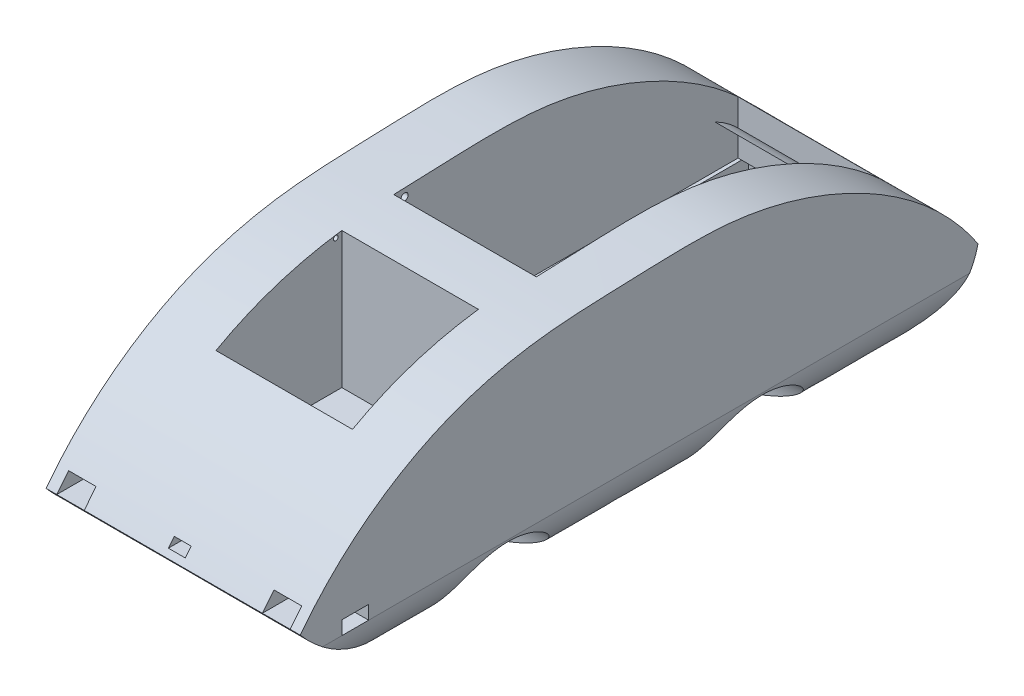
SolidWorks part; units mm, degrees
ref_plane "Front Plane" through (0, 0, 0) normal (0, 0, 1) x (1, 0, 0)
ref_plane "Top Plane" through (0, 0, 0) normal (0, 1, 0) x (1, 0, 0)
ref_plane "Right Plane" through (0, 0, 0) normal (1, 0, 0) x (0, 0, -1)
sketch "Sketch1" plane through (0, 0, 0) normal (1, 0, 0) x (0, 0, -1)
  line L0 (126.9231, -20.896) -> (148.2112, -20.896)
  arc A0 (57.2036, -21.3378) -> (41.2372, -20.4994) centre (49.2045, -21.2225) ccw
  arc A1 (117.2045, -21.2077) -> (101.2105, -20.8977) centre (109.2045, -21.2094) ccw
  spline S0 degree 1 poles (0, 0) (160, 0) knots 0 0 1 1
  spline S1 degree 3 poles (0, 0) (7.469, -8.9747) (25.4807, -16.1765) (37.8251, -20.037) (41.2372, -20.4994) knots 0 0 0 0 0.212367 0.271912 0.271912 0.271912 0.271912
  spline S2 degree 3 poles (0, 0) (9.0863, 11.9008) (27.1721, 25.9258) (56.0071, 32.9786) (78.6576, 33.4535) (102.9739, 34.7126) (133.2674, 26.0982) (151.942, 12.1514) (160, 0) knots 0 0 0 0 0.24914 0.361443 0.486953 0.62448 0.76252 1 1 1 1
  spline S3 degree 1 poles (57.2036, -21.3378) (101.2105, -20.8977) knots 0 0 1 1
  spline S4 degree 3 poles (117.2045, -21.2077) (120.6446, -21.3315) (129.5303, -21.3564) (143.0313, -16.1544) (155.397, -9.6529) (159.2255, -3.6168) (160, 0) knots 0.704703 0.704703 0.704703 0.704703 0.763972 0.874905 0.943377 1 1 1 1
  dimension "D1" = 16
  dimension "D2" = 16
  dimension "D3" = 160
  dimension "D4" = 60
  dimension "D6" = 160
  dimension "D7" = 11.0964
  dimension "D5" = 113
sketch "Sketch6" plane through (0, 0, 0) normal (1, 0, 0) x (0, 0, -1)
extrude "Boss-Extrude6" add sketch "Sketch1" along normal blind 60 contours A1 S4 S0 S1 A0 S3 | S2 S0 region at (0, -8.9953, -82.9979) region at (0, 14.336, -80.6046)
sketch "Sketch7" plane through (0, 0, 0) normal (0, 0, 1) x (1, 0, 0)
  line L0 (0, 0) -> (0, -20.4994) construction
  line L1 (60, -20.4994) -> (0, -20.4994) construction
  line L2 (15.1156, -20.4994) -> (11.2601, -27.1566)
  line L3 (11.2601, -27.1566) -> (-10.1442, -25.5613)
  line L4 (-10.1442, -25.5613) -> (-11.2884, -14.098)
  line L5 (-11.2884, -14.098) -> (-8.1517, 1.1709)
  line L6 (-8.1517, 1.1709) -> (0, 0)
  spline S0 degree 2 poles (0, 0) (-1.7812, -14.0651) (15.1156, -20.4994) knots 0 0 0 1 1 1
extrude "Cut-Extrude7" cut sketch "Sketch7" against normal blind 184
sketch "Sketch8" plane through (0, 0, 0) normal (0, 0, 1) x (1, 0, 0)
  line L0 (60, -20.4994) -> (60, 0) construction
  line L1 (60, -20.4994) -> (15.1156, -20.4994) construction
  line L2 (45.1087, -20.4994) -> (46.7098, -23.4484)
  line L3 (46.7098, -23.4484) -> (65.3517, -25.8502)
  line L4 (65.3517, -25.8502) -> (67.7534, -15.4427)
  line L5 (67.7534, -15.4427) -> (63.9793, -2.2905)
  line L6 (63.9793, -2.2905) -> (60, 0)
  spline S0 degree 2 poles (60, 0) (61.7463, -13.956) (45.1087, -20.4994) knots 0 0 0 1 1 1
extrude "Cut-Extrude8" cut sketch "Sketch8" against normal blind 184
sketch "Sketch9" plane through (0, 0, 0) normal (1, 0, 0) x (0, 0, -1)
  line L4 (101.236, -20.4994) -> (104.6343, -23.8977)
  line L5 (104.6343, -23.8977) -> (51.4249, -23.1758)
  line L6 (51.4249, -23.1758) -> (57.1717, -20.4994)
  spline S0 degree 1 poles (57.1717, -20.4994) (101.236, -20.4994) knots 0 0 1 1
extrude "Cut-Extrude9" cut sketch "Sketch9" along normal blind 120
sketch "Sketch10" plane through (0, 0, 0) normal (1, 0, 0) x (0, 0, -1)
  line L0 (129.235, -20.4994) -> (128.462, -23.4248)
  line L1 (128.462, -23.4248) -> (116.148, -22.8353)
  line L2 (116.148, -22.8353) -> (115.0345, -20.4994)
  line L3 (115.0345, -20.4994) -> (117.1729, -20.4994)
  spline S0 degree 1 poles (117.1729, -20.4994) (129.235, -20.4994) knots 0 0 1 1
extrude "Cut-Extrude10" cut sketch "Sketch10" along normal blind 92
sketch "Sketch11" plane through (0, 0, 0) normal (0, 1, 0) x (1, 0, 0)
  line L0 (30, 160) -> (30, 0) construction
  line L1 (60, 160) -> (0, 160) construction
  line L2 (60, 0) -> (0, 0) construction
  line L3 (30, 80) -> (0, 80) construction
  line L4 (0, 160) -> (0, 0) construction
  line L5 (30, 80) -> (60, 80) construction
  line L6 (60, 0) -> (60, 160) construction
  line L7 (45, 80) -> (45, 167.0589) construction
  line L8 (15, 80) -> (15, -2.0029) construction
  line L9 (45, 80) -> (45, -2.0029) construction
  line L10 (15, 80) -> (15, 160) construction
  line L12 (15, 63.6141) -> (45, 63.6141)
  line L13 (15, 63.6141) -> (15, 150.7872)
  line L14 (15, 150.7872) -> (45, 150.7872)
  line L15 (45, 63.6141) -> (45, 150.7872)
extrude "Cut-Extrude11" cut sketch "Sketch11" against normal blind 10
sketch "Sketch12" plane through (0, 0, 0) normal (0, 1, 0) x (1, 0, 0)
  line L0 (28.3313, 160) -> (28.3313, 0) construction
  line L1 (60, 160) -> (0, 160) construction
  line L2 (28.3313, 80) -> (0, 80) construction
  line L3 (28.3313, 80) -> (60, 80) construction
  line L4 (44.1657, 80) -> (44.1657, 160) construction
  line L5 (14.1657, 80) -> (14.1657, 160) construction
  line L7 (14.1657, 149.2065) -> (47.8219, 149.2065)
  line L8 (14.1657, 149.2065) -> (14.1657, 67.923)
  line L9 (14.1657, 67.923) -> (47.8219, 67.923)
  line L10 (47.8219, 149.2065) -> (47.8219, 67.923)
  dimension "D1" = 33.6562
extrude "Cut-Extrude12" cut sketch "Sketch12" along normal blind 52
sketch "Sketch13" plane through (0, 0, 0) normal (0, 1, 0) x (1, 0, 0)
  line L1 (14.3184, 55.5097) -> (46.5508, 55.5097)
  line L2 (14.3184, 55.5097) -> (14.3184, 25.8054)
  line L3 (14.3184, 25.8054) -> (46.5508, 25.8054)
  line L4 (46.5508, 55.5097) -> (46.5508, 25.8054)
  dimension "D1" = 32.2323
  dimension "D2" = 29.7043
extrude "Cut-Extrude13" cut sketch "Sketch13" along normal blind 76
sketch "Sketch14" plane through (0, 0, 0) normal (0, 1, 0) x (1, 0, 0)
  line L0 (14.2315, 121.7629) -> (24.3195, 121.7629) construction
  line L1 (41.3475, 118.8525) -> (41.3475, 131.5192) construction
  line L2 (44.678, 121.7629) -> (34.7309, 121.7629) construction
  line L3 (24.3195, 118.8525) -> (24.3195, 121.3601) construction
  line L4 (34.7309, 118.8525) -> (34.7309, 127.8775) construction
  line L6 (24.3195, 121.7629) -> (34.7309, 121.7629)
  line L7 (24.3195, 121.7629) -> (24.3195, 127.8775)
  line L8 (24.3195, 127.8775) -> (34.7309, 127.8775)
  line L9 (34.7309, 121.7629) -> (34.7309, 127.8775)
extrude "Cut-Extrude14" cut sketch "Sketch14" against normal blind 80 and the other way blind 58
sketch "Sketch15" plane through (0, 0, 0) normal (0, 1, 0) x (1, 0, 0)
  line L0 (19.5217, 101.236) -> (19.5217, 80.2082) construction
  line L1 (45.1087, 101.236) -> (15.1156, 101.236) construction
  line L2 (37.4565, 101.236) -> (37.4565, 72.8879) construction
  line L3 (15.1156, 80.2082) -> (45.1087, 80.2082) construction
  line L4 (15.1156, 101.236) -> (15.1156, 57.1717) construction
  line L5 (45.1087, 101.236) -> (45.1087, 57.1717) construction
  line L6 (45.1087, 72.8879) -> (14.1535, 72.8879) construction
  line L7 (24.3195, 121.7629) -> (24.3195, 66.3413) construction
  line L8 (34.7309, 121.7629) -> (34.7309, 58.642) construction
  line L10 (24.3195, 72.8879) -> (34.7309, 72.8879)
  line L11 (24.3195, 72.8879) -> (24.3195, 80.2082)
  line L12 (24.3195, 80.2082) -> (34.7309, 80.2082)
  line L13 (34.7309, 72.8879) -> (34.7309, 80.2082)
extrude "Cut-Extrude15" cut sketch "Sketch15" against normal blind 61 and the other way blind 55
sketch "Sketch16" plane through (0, 0, 0) normal (1, 0, 0) x (0, 0, -1)
  line L0 (41.2372, -20.4994) -> (57.1717, -20.4994)
  circle A0 centre (49.2045, -20.4994) radius 15
  dimension "D1" = 30
extrude "Cut-Extrude17" cut sketch "Sketch16" against normal blind 56 and the other way blind 12 contours A0
sketch "Sketch17" plane through (0, 0, 0) normal (1, 0, 0) x (0, 0, -1)
  line L0 (101.236, -20.4994) -> (117.1729, -20.4994)
  circle A0 centre (109.2045, -20.4994) radius 15
  dimension "D1" = 30
extrude "Cut-Extrude18" cut sketch "Sketch17" against normal blind 17 and the other way blind 14 contours A0
sketch "Sketch19" plane through (0, 0, 0) normal (1, 0, 0) x (0, 0, -1)
  line L0 (41.2372, -20.4994) -> (57.1717, -20.4994)
  circle A3 centre (49.2045, -20.4994) radius 15
  dimension "D1" = 30
extrude "Cut-Extrude20" cut sketch "Sketch19" against normal blind 2 and the other way blind 65 contours A3
sketch "Sketch20" plane through (0, 0, 0) normal (1, 0, 0) x (0, 0, -1)
  line L0 (101.236, -20.4994) -> (117.1729, -20.4994)
  circle A0 centre (109.2045, -20.4994) radius 15
  dimension "D1" = 30
extrude "Cut-Extrude21" cut sketch "Sketch20" against normal blind 17 and the other way blind 64 contours A0
sketch "Sketch24" plane through (0, 0, 0) normal (1, 0, 0) x (0, 0, -1)
  line L0 (68.091, 32.8945) -> (68.091, 29.8945)
  line L1 (68.091, 32.8945) -> (72.091, 33.0999)
  line L2 (68.091, 31.3945) -> (70.4684, 31.3945)
  circle A1 centre (70.4684, 31.3945) radius 0.85
  circle A2 centre (81.5076, 38.3352) radius 0.85
  dimension "D3" = 1.7
  dimension "D1" = 4
  dimension "D2" = 3
extrude "Cut-Extrude27" cut sketch "Sketch24" against normal blind 47 and the other way blind 58 contours A1
sketch "Sketch25" plane through (0, 0, 0) normal (1, 0, 0) x (0, 0, -1)
  circle A0 centre (70.4684, 31.3945) radius 0.85
extrude "Boss-Extrude7" add sketch "Sketch25" along normal blind 1
sketch "Sketch26" plane through (0, 0, 0) normal (1, 0, 0) x (0, 0, -1)
  spline S3 degree 1 poles (144.4587, 10.8047) (150.0644, 5.2892) knots 0 0 1 1
extrude "Extrude-Thin2" add sketch "Sketch26" along normal blind 56 thin thin type one direction wall 1
fillet "Fillet2" radius 20 1 edges at (30.9938, 10.8047, -144.4587)
sketch "Sketch35" plane through (0, 0, 0) normal (1, 0, 0) x (0, 0, -1)
  line L0 (55.238, 32.0798) -> (54.5577, 21.6054)
  line L1 (55.1863, 31.2835) -> (54.0869, 31.2835)
  circle A0 centre (54.0869, 31.2835) radius 0.5578
  spline S0 degree 3 poles (0, 0) (9.0863, 11.9008) (27.1721, 25.9258) (56.0071, 32.9786) (78.6576, 33.4535) (102.9739, 34.7126) (133.2674, 26.0982) (151.942, 12.1514) (160, 0) knots 0 0 0 0 0.24914 0.361443 0.486953 0.62448 0.76252 1 1 1 1 construction
extrude "Cut-Extrude30" cut sketch "Sketch35" along normal blind 52 and the other way blind 1 contours A0
sketch "Sketch36" plane through (0, 0, 0) normal (0, 0, 1) x (1, 0, 0)
  line L0 (60, 0) -> (0, 0) construction
  line L1 (2.537, 0) -> (9.0175, 0)
  line L2 (2.537, 0) -> (2.537, 3.4779)
  line L3 (2.537, 3.4779) -> (9.0175, 3.4779)
  line L4 (9.0175, 0) -> (9.0175, 3.4779)
extrude "Cut-Extrude31" cut sketch "Sketch36" against normal blind 7
sketch "Sketch37" plane through (0, 0, 0) normal (0, 0, 1) x (1, 0, 0)
  line L0 (60, 0) -> (9.0175, 0) construction
  line L8 (57.6233, 0) -> (51.0737, 0)
  line L9 (57.6233, 0) -> (57.6233, 3.401)
  line L10 (57.6233, 3.401) -> (51.0737, 3.401)
  line L11 (51.0737, 0) -> (51.0737, 3.401)
extrude "Cut-Extrude32" cut sketch "Sketch37" against normal blind 7 and the other way blind 21
sketch "Sketch38" plane through (0, 0, 0) normal (1, 0, 0) x (0, 0, -1)
  line L0 (158.0341, -5.0353) -> (5.2459, -5.0353) construction
  line L1 (8.839, -5.0353) -> (15.2052, -5.0353)
  line L2 (8.839, -5.0353) -> (8.839, -1.7535)
  line L3 (8.839, -1.7535) -> (15.2052, -1.7535)
  line L4 (15.2052, -5.0353) -> (15.2052, -1.7535)
extrude "Cut-Extrude33" cut sketch "Sketch38" against normal blind 10 and the other way blind 7
ref_plane "Plane1" through (70, 0, 0) normal (1, 0, 0) x (0, 0, -1)
sketch "Sketch39" plane through (70, 0, 0) normal (1, 0, 0) x (0, 0, -1)
  line L0 (158.0341, -5.0353) -> (5.2459, -5.0353) construction
  line L2 (9.9115, -5.0353) -> (16.159, -5.0353)
  line L3 (9.9115, -5.0353) -> (9.9115, -1.7933)
  line L4 (9.9115, -1.7933) -> (16.159, -1.7933)
  line L5 (16.159, -5.0353) -> (16.159, -1.7933)
extrude "Cut-Extrude34" cut sketch "Sketch39" against normal blind 17 and the other way blind 14
sketch "Sketch42" plane through (0, 0, 0) normal (0, 0, 1) x (1, 0, 0)
  line L0 (51.0737, 0) -> (9.0175, 0) construction
  line L5 (30.0456, 0) -> (30.0456, 15.1158) construction
  line L6 (27.9209, 1.239) -> (31.9209, 1.239)
  line L7 (27.9209, 1.239) -> (27.9209, 3.739)
  line L8 (27.9209, 3.739) -> (31.9209, 3.739)
  line L9 (31.9209, 1.239) -> (31.9209, 3.739)
  dimension "D1" = 2.5
extrude "Cut-Extrude35" cut sketch "Sketch42" against normal blind 1.6 contours L6 L9 L8 L7
sketch "Sketch43" plane through (0, 0, 0) normal (0, 0, 1) x (1, 0, 0)
  line L1 (27.9209, 1.239) -> (31.9209, 1.239)
  line L2 (27.9209, 1.239) -> (27.9209, 2.9573)
  line L3 (27.9209, 2.9573) -> (31.9209, 2.9573)
  line L4 (31.9209, 1.239) -> (31.9209, 2.9573)
extrude "Cut-Extrude36" cut sketch "Sketch43" against normal blind 2.6
sketch "Sketch44" plane through (0, 0, 0) normal (0, 0, 1) x (1, 0, 0)
  line L0 (31.9209, 1.239) -> (31.9209, 2.9573) construction
  line L1 (27.9209, 1.239) -> (31.9209, 1.239)
  line L2 (27.9209, 1.239) -> (27.9209, 2.8759)
  line L3 (27.9209, 2.8759) -> (31.9209, 2.8759)
  line L4 (31.9209, 1.239) -> (31.9209, 2.8759)
extrude "Cut-Extrude37" cut sketch "Sketch44" against normal blind 4.6
